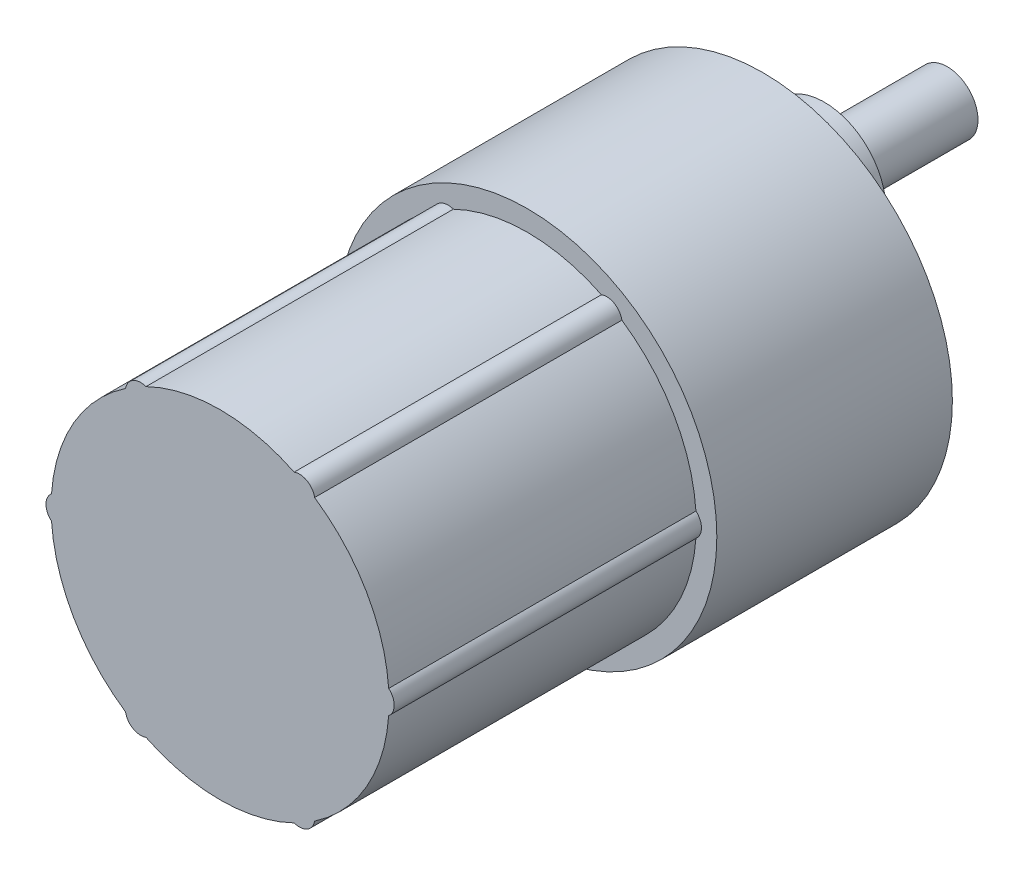
SolidWorks part; units mm, degrees
ref_plane "前视基准面" through (0, 0, 0) normal (0, 0, 1) x (1, 0, 0)
ref_plane "上视基准面" through (0, 0, 0) normal (0, 1, 0) x (1, 0, 0)
ref_plane "右视基准面" through (0, 0, 0) normal (1, 0, 0) x (0, 0, -1)
sketch "草图1" plane through (0, 0, 0) normal (0, 0, 1) x (1, 0, 0)
  circle A0 centre (0, 0) radius 18.5
  circle A1 centre (0, 0) radius 15.5 construction
  circle A2 centre (0, 0) radius 16.5
  circle A3 centre (-15.5, 0) radius 1.5
  circle A4 centre (-7.75, 13.4234) radius 1.5
  circle A5 centre (7.75, 13.4234) radius 1.5
  circle A6 centre (15.5, 0) radius 1.5
  circle A7 centre (7.75, -13.4234) radius 1.5
  circle A8 centre (-7.75, -13.4234) radius 1.5
  circle A9 centre (0, 7) radius 3
  circle A10 centre (0, 7) radius 6
  point P19 (0, 0)
  dimension "D1" = 37
  dimension "D2" = 31
  dimension "D3" = 33
  dimension "D4" = 3
  dimension "D6" = 6
  dimension "D7" = 7
  dimension "D8" = 12
  dimension "D5" = 6
extrude "凸台-拉伸1" add sketch "草图1" along normal blind 23 contours A0 A8 A2 A3 A4 A5 A6 A7 | A8 A2 A7 A6 A5 A4 A3 A10 | A10 A9 | A9 region at (-17.9767, 0, 0) region at (0, -1.1236, 0) region at (0, 7, 0) region at (-5.8303, 7, 0)
extrude "凸台-拉伸2" add sketch "草图1<3>" against normal blind 6 contours A10 A9 region at (-5.8303, 7, 0)
sketch "草图1<3>" plane through (0, 0, 0) normal (0, 0, 1) x (1, 0, 0) same geometry as "草图1"
extrude "凸台-拉伸3" add sketch "草图1<4>" against normal blind 18 contours A9 region at (0, 7, 0)
sketch "草图1<4>" plane through (0, 0, 0) normal (0, 0, 1) x (1, 0, 0) same geometry as "草图1"
extrude "凸台-拉伸5" add sketch "草图1<5>" along normal blind 53 contours A2 A4 | A2 A4 | A2 A3 | A2 A3 | A2 A8 | A2 A7 | A2 A7 | A2 A5 | A2 A6 | A2 A5 | A8 A2 A7 A6 A5 A4 A3 A10 | A10 A9 | A9 | A8 | A6 region at (15.3466, 0, 0) region at (0, -1.1236, 0) region at (7.6733, 13.2906, 0) region at (8.3476, 14.4585, 0) region at (8.3476, -14.4585, 0) region at (7.6733, -13.2906, 0) region at (-7.6733, 13.2906, 0) region at (-8.3476, 14.4585, 0) region at (-7.6733, -13.2906, 0) region at (-15.3466, 0, 0) region at (-16.6952, 0, 0) region at (0, 7, 0) region at (-5.8303, 7, 0)
sketch "草图1<5>" plane through (0, 0, 0) normal (0, 0, 1) x (1, 0, 0) same geometry as "草图1"
extrude "切除-拉伸3" cut sketch "草图1<6>" along normal blind 10 contours A2 A6 | A2 A6 | A2 A7 | A2 A8 | A2 A8 | A2 A3 | A2 A3 | A2 A5 | A2 A5 | A2 A4 | A2 A4 | A2 A7 region at (15.3466, 0, 0) region at (16.6952, 0, 0) region at (7.6733, 13.2906, 0) region at (8.3476, 14.4585, 0) region at (8.3476, -14.4585, 0) region at (7.6733, -13.2906, 0) region at (-7.6733, 13.2906, 0) region at (-8.3476, 14.4585, 0) region at (-8.3476, -14.4585, 0) region at (-7.6733, -13.2906, 0) region at (-15.3466, 0, 0) region at (-16.6952, 0, 0)
sketch "草图1<6>" plane through (0, 0, 0) normal (0, 0, 1) x (1, 0, 0) same geometry as "草图1"
